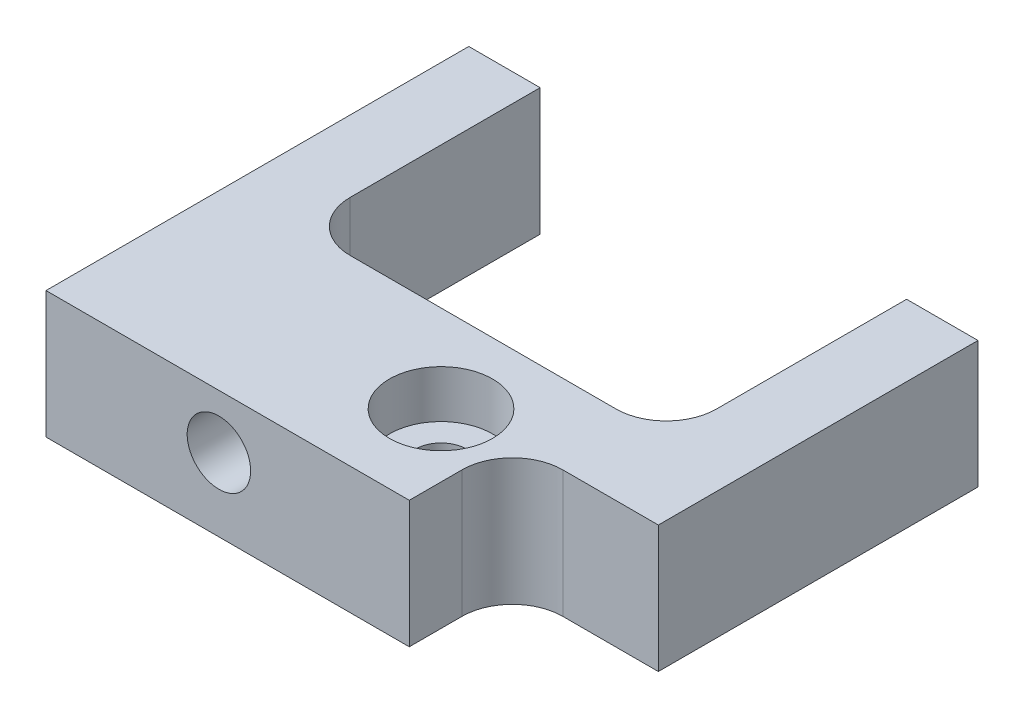
SolidWorks part; units mm, degrees
material "PTFE (general)"
ref_plane "Front" through (0, 0, 0) normal (0, 0, 1) x (1, 0, 0)
ref_plane "Top" through (0, 0, 0) normal (0, 1, 0) x (1, 0, 0)
ref_plane "Right" through (0, 0, 0) normal (1, 0, 0) x (0, 0, -1)
ref_axis "X" through (-80.9, 0, 0) along (1, 0, 0)
ref_axis "Y" through (0, -50, 0) along (0, 1, 0)
ref_axis "Z" through (0, 0, -80.9) along (0, 0, 1)
sketch "Sketch1" plane through (0, 0, 0) normal (0, 1, 0) x (1, 0, 0)
  line L0 (12, 0.5) -> (12, -6)
  line L1 (12, -6) -> (-10.9, -6)
  line L2 (-10.9, -6) -> (-10.9, 20.65)
  line L3 (-10.9, 20.65) -> (-6.4, 20.65)
  line L4 (16.7, 5.5) -> (-6.4, 5.5)
  line L5 (-6.4, 5.5) -> (-6.4, 20.65)
  line L8 (21.2, 20.65) -> (16.7, 20.65)
  line L10 (16.7, 20.65) -> (16.7, 5.5)
  line L11 (21.2, 20.65) -> (21.2, 0.5)
  line L13 (21.2, 0.5) -> (12, 0.5)
  dimension "D1" = 12
  dimension "D2" = 6
  dimension "D3" = 26.65
  dimension "D4" = 5.5
  dimension "D5" = 10.9
  dimension "D6" = 32.1
  dimension "D7" = 4.5
  dimension "D8" = 5
extrude "Boss-Extrude1" add sketch "Sketch1" along normal mid plane 8
fillet "Fillet1" radius 3.175 3 edges at (12, 0, -0.5) (16.7, 0, -5.5) (-6.4, 0, -5.5)
sketch "Sketch2" plane through (0, 0, 0) normal (0, 0, 1) x (1, 0, 0)
  line L0 (0, 0) -> (0, 0.6) construction
  circle A0 centre (0, 0.6) radius 2
  dimension "D2" = 4
  dimension "D1" = 0.6
extrude "Cut-Extrude1" cut sketch "Sketch2" against normal through all both and the other way through all
sketch "Sketch3" plane through (0, 0, 0) normal (1, 0, 0) x (0, 0, -1)
  line L0 (0, -0.6) -> (0, 0) construction
  circle A0 centre (0, -0.6) radius 2
  dimension "D2" = 4
  dimension "D1" = 0.6
extrude "Cut-Extrude2" cut sketch "Sketch3" against normal through all and the other way blind 4.5
hole_wizard "Ø1.5 (1.5) Diameter Hole1" positions "Sketch4" profile "Sketch5" hole size "Ø1.5" standard "ANSI Metric"
sketch "Sketch4" plane through (0, 0, -20.65) normal (0, 0, -1) x (-1, 0, 0)
  line L0 (-19.05, 0.6) -> (8.75, 0.6) construction
  line L3 (-19.05, 0.6) -> (-21.2, 0.6) construction
  line L4 (-21.2, 4) -> (-21.2, -4) construction
  line L7 (8.75, 0.6) -> (10.9, 0.6) construction
  line L8 (10.9, 4) -> (10.9, -4) construction
  line L10 (6.4, 4) -> (10.9, 4) construction
  point P0 (-19.05, 0.6)
  point P2 (8.75, 0.6)
  dimension "D1" = 3.4
  dimension "D2" = 27.8
sketch "Sketch5" plane through (19.05, 0.6, -20.65) normal (1, 0, 0) x (0, 1, 0)
  line L0 (0, 0) -> (0, 7.4506)
  line L1 (0, 7.4506) -> (0.75, 7)
  line L2 (0.75, 7) -> (0.75, 0)
  line L5 (0.75, 0) -> (0, 0)
  line L10 (0, 7.4506) -> (-0.75, 7) construction
  line L11 (0, -6.35) -> (0, 107.95) construction
  dimension "Hole Dia." = 1.5
  dimension "Hole Depth" = 7
  dimension "Drill Angle" = 118
hole_wizard "CBORE for M3 SHCS1" positions "Sketch6" profile "Sketch7" counterbore size "M3" standard "ANSI Metric" end condition up to next
sketch "Sketch6" plane through (0, 4, 0) normal (0, 1, 0) x (1, 0, 0)
  line L0 (0, 0) -> (8, 0) construction
  point P0 (8, 0)
  dimension "D1" = 8
sketch "Sketch7" plane through (8, 4, 0) normal (1, 0, 0) x (0, 0, 1)
  line L0 (0, 0) -> (0, 8)
  line L1 (0, 8) -> (1.6, 8)
  line L3 (1.6, 8) -> (1.6, 3)
  line L4 (1.6, 3) -> (3.25, 3)
  line L5 (3.25, 3) -> (3.25, 0)
  line L7 (3.25, 0) -> (0, 0)
  line L11 (0, -6.35) -> (0, 107.95) construction
  dimension "Thru Hole Dia." = 3.2
  dimension "Thru Hole Depth" = 8
  dimension "C'Bore Dia." = 6.5
  dimension "C'Bore Depth" = 3
